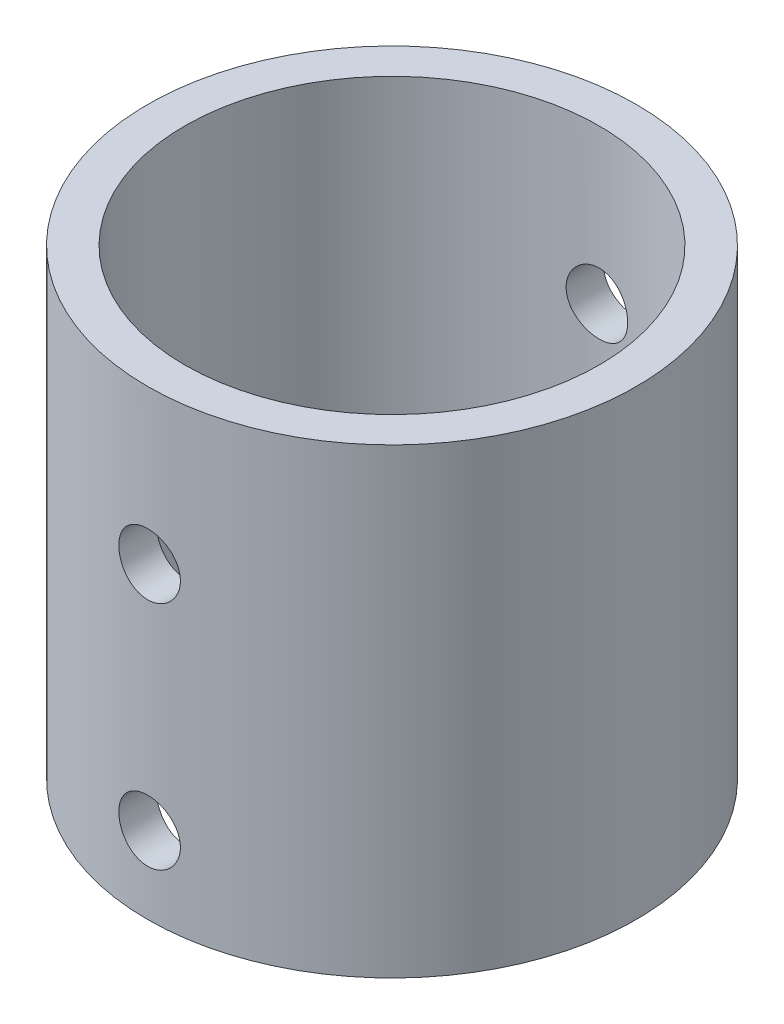
SolidWorks part; units mm, degrees
ref_plane "Front Plane" through (0, 0, 0) normal (0, 0, 1) x (1, 0, 0)
ref_plane "Top Plane" through (0, 0, 0) normal (0, 1, 0) x (1, 0, 0)
ref_plane "Right Plane" through (0, 0, 0) normal (1, 0, 0) x (0, 0, -1)
sketch "Sketch1" plane through (0, 0, 0) normal (0, 1, 0) x (1, 0, 0)
  circle A0 centre (0, 0) radius 13.462
  circle A1 centre (0, 0) radius 15.875
  dimension "D1" = 31.75
  dimension "D2" = 2.413
extrude "Boss-Extrude1" add sketch "Sketch1" against normal blind 30
sketch "Sketch2" plane through (0, 0, 0) normal (0, 0, 1) x (1, 0, 0)
  line L0 (0, 0) -> (0, -30) construction
  line L1 (-15.875, -30) -> (15.875, -30) construction
  circle A0 centre (0, -25) radius 2
  circle A1 centre (0, -10) radius 2
  dimension "D1" = 4
  dimension "D2" = 10
  dimension "D3" = 15
  dimension "D4" = 5
extrude "Cut-Extrude1" cut sketch "Sketch2" against normal blind 30 and the other way blind 30
